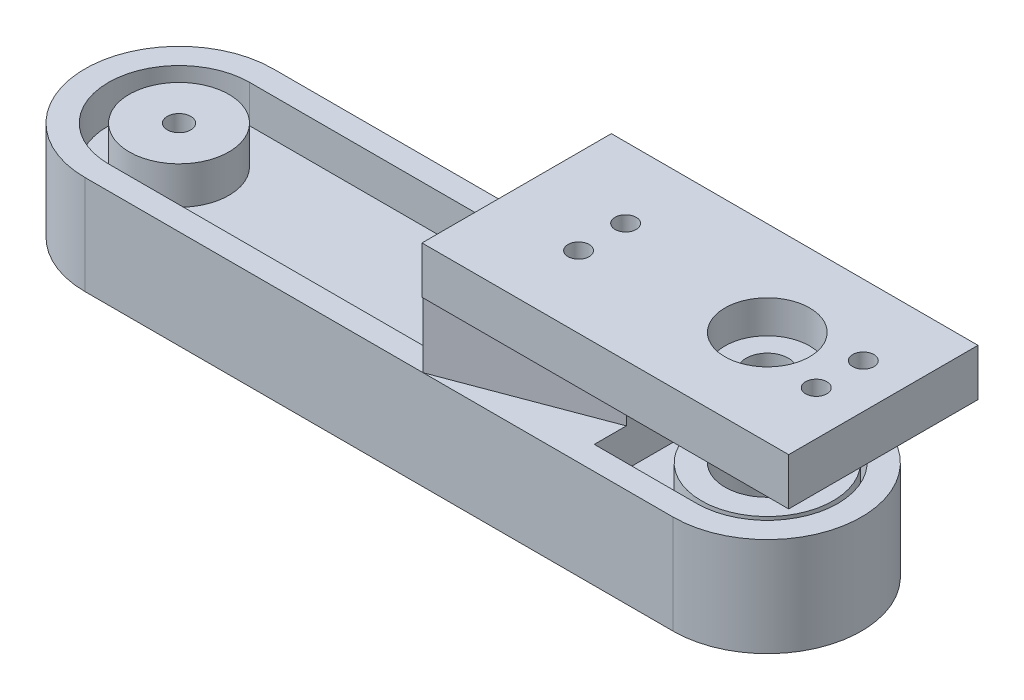
SolidWorks part; units mm, degrees
ref_plane "Front Plane" through (0, 0, 0) normal (0, 0, 1) x (1, 0, 0)
ref_plane "Top Plane" through (0, 0, 0) normal (0, 1, 0) x (1, 0, 0)
ref_plane "Right Plane" through (0, 0, 0) normal (1, 0, 0) x (0, 0, -1)
sketch "Sketch1" plane through (0, 0, 0) normal (0, 1, 0) x (1, 0, 0)
  line L0 (-62.5, 0) -> (62.5, 0) construction
  line L1 (-62.5, 30) -> (62.5, 30)
  line L2 (-62.5, -30) -> (62.5, -30)
  line L3 (-62.5, 0) -> (62.5, 0) construction
  line L4 (-62.5, 15) -> (62.5, 15)
  line L5 (-62.5, -15) -> (62.5, -15)
  arc A0 (-62.5, 30) -> (-62.5, -30) centre (-62.5, 0) ccw
  arc A1 (62.5, -30) -> (62.5, 30) centre (62.5, 0) ccw
  arc A2 (-62.5, 15) -> (-62.5, -15) centre (-62.5, 0) ccw
  arc A3 (62.5, -15) -> (62.5, 15) centre (62.5, 0) ccw
  point P3 (0, 0)
  point P8 (0, 0)
  dimension "D1" = 60
  dimension "D2" = 125
  dimension "D3" = 15
extrude "Boss-Extrude1" add sketch "Sketch1" along normal blind 25 contours L2 A1 L1 A0
sketch "Sketch4" plane through (0, 25, 0) normal (0, 1, 0) x (1, 0, 0)
  line L0 (-62.5, 30) -> (62.5, 30) construction
  circle A0 centre (-62.5, 0) radius 2.5
  dimension "D1" = 5
  dimension "D2" = 30
  dimension "D3" = 62.5
extrude "Cut-Extrude1" cut sketch "Sketch4" against normal through all
extrude "Cut-Extrude2" cut sketch "Sketch1<3>" against normal through all and the other way blind 10 contours L5 A3 L4 A2
sketch "Sketch1<3>" plane through (0, 0, 0) normal (0, 1, 0) x (1, 0, 0) same geometry as "Sketch1"
ref_plane "Plane1" through (0, 25, 0) normal (0, 1, 0) x (1, 0, 0)
sketch "Sketch7" plane through (0, 25, 0) normal (0, 1, 0) x (1, 0, 0)
  line L0 (-62.5, 0) -> (62.5, 0) construction
  line L1 (-62.5, 15) -> (62.5, 15)
  line L2 (-62.5, -15) -> (62.5, -15)
  line L3 (-62.5, 30) -> (62.5, 30) construction
  arc A0 (-62.5, 15) -> (-62.5, -15) centre (-62.5, 0) ccw
  arc A1 (62.5, -15) -> (62.5, 15) centre (62.5, 0) ccw
  point P4 (0, 0)
  dimension "D1" = 15
extrude "Cut-Extrude3" cut sketch "Sketch7" against normal blind 10
sketch "Sketch8" plane through (0, 10, 0) normal (0, -1, 0) x (-1, 0, 0)
  line L0 (-62.5, 15) -> (62.5, 15) construction
  circle A0 centre (-62.5, 0) radius 9
  dimension "D3" = 18
  dimension "D1" = 15
  dimension "D2" = 62.5
extrude "Cut-Extrude5" cut sketch "Sketch8" against normal through all
sketch "Sketch9" plane through (0, 15, 0) normal (0, 1, 0) x (1, 0, 0)
  circle A0 centre (-62.5, 0) radius 10.5959
  circle A1 centre (-62.5, 0) radius 2.5
sketch "Sketch10" plane through (0, 25, 0) normal (0, 1, 0) x (1, 0, 0)
  line L0 (-62.5, 20) -> (62.5, 20)
  line L1 (-62.5, -20) -> (62.5, -20)
  line L2 (-62.5, -30) -> (62.5, -30) construction
  line L3 (-62.5, 30) -> (62.5, 30) construction
  line L4 (-62.5, -30) -> (62.5, -30)
  line L5 (-62.5, 30) -> (62.5, 30)
  arc A0 (-62.5, 20) -> (-62.5, -20) centre (-62.5, 0) ccw
  arc A1 (62.5, -20) -> (62.5, 20) centre (62.5, 0) ccw
  arc A2 (-62.5, 30) -> (-62.5, -30) centre (-62.5, 0) ccw construction
  arc A3 (62.5, -30) -> (62.5, 30) centre (62.5, 0) ccw construction
  arc A4 (-62.5, 30) -> (-62.5, -30) centre (-62.5, 0) ccw
  arc A5 (62.5, -30) -> (62.5, 30) centre (62.5, 0) ccw
  dimension "D1" = 40
  dimension "D2" = 40
extrude "Cut-Extrude6" cut sketch "Sketch10" against normal up to next
sketch "Sketch11" plane through (0, 15, 0) normal (0, 1, 0) x (1, 0, 0)
  circle A0 centre (62.5, 0) radius 9
  circle A1 centre (62.5, 0) radius 14
  dimension "D1" = 28
  dimension "D2" = 18
extrude "Boss-Extrude3" add sketch "Sketch11" along normal blind 8 and the other way blind 14
extrude "Boss-Extrude4" add sketch "Sketch9" along normal blind 8 and the other way blind 14 contours A0
sketch "Sketch12" plane through (0, 1, 0) normal (0, -1, 0) x (1, 0, 0)
  circle A0 centre (-62.5, 0) radius 2.5
extrude "Cut-Extrude7" cut sketch "Sketch12" against normal through all
sketch "Sketch13" plane through (0, 25, 0) normal (0, 1, 0) x (1, 0, 0)
  line L1 (92.0948, 31.5917) -> (-101.7934, 31.5917)
  line L2 (92.0948, 31.5917) -> (92.0948, -40.9372)
  line L3 (92.0948, -40.9372) -> (-101.7934, -40.9372)
  line L4 (-101.7934, 31.5917) -> (-101.7934, -40.9372)
extrude "Cut-Extrude8" cut sketch "Sketch13" against normal blind 2
sketch "Sketch14" plane through (0, 0, 0) normal (0, -1, 0) x (1, 0, 0)
  line L1 (99.5163, 27.7947) -> (-99.2633, 27.7947)
  line L2 (99.5163, 27.7947) -> (99.5163, -35.2041)
  line L3 (99.5163, -35.2041) -> (-99.2633, -35.2041)
  line L4 (-99.2633, 27.7947) -> (-99.2633, -35.2041)
extrude "Cut-Extrude9" cut sketch "Sketch14" against normal blind 2
sketch "Sketch15" plane through (0, 15, 0) normal (0, 1, 0) x (1, 0, 0)
  line L0 (62.5, 20) -> (-62.5, 20) construction
  line L1 (40.7342, 20) -> (9.3613, 20)
  line L2 (40.7342, 20) -> (40.7342, -20)
  line L3 (40.7342, -20) -> (9.3613, -20)
  line L4 (9.3613, 20) -> (9.3613, -20)
  line L5 (-62.5, -20) -> (62.5, -20) construction
extrude "Boss-Extrude6" add sketch "Sketch15" along normal blind 22
sketch "Sketch16" plane through (0, 37, 0) normal (0, 1, 0) x (1, 0, 0)
  line L1 (9.3613, 20) -> (87.2738, 20)
  line L2 (9.3613, 20) -> (9.3613, -20.2336)
  line L3 (9.3613, -20.2336) -> (87.2738, -20.2336)
  line L4 (87.2738, 20) -> (87.2738, -20.2336)
extrude "Boss-Extrude7" add sketch "Sketch16" along normal blind 10
sketch "Sketch17" plane through (0, 37, 0) normal (0, -1, 0) x (1, 0, 0)
  circle A0 centre (62.5, 0) radius 9
  dimension "D1" = 18
extrude "Cut-Extrude10" cut sketch "Sketch17" against normal blind 10
sketch "Sketch18" plane through (0, 47, 0) normal (0, 1, 0) x (1, 0, 0)
  line L0 (27.4, -5) -> (27.4, 5) construction
  line L1 (62.5, 0) -> (15.5374, 0) construction
  line L2 (77.9, 5) -> (77.9, -5) construction
  circle A0 centre (27.4, 5) radius 2.25
  circle A1 centre (27.4, -5) radius 2.25
  circle A2 centre (77.9, 5) radius 2.25
  circle A3 centre (77.9, -5) radius 2.25
  point P7 (27.4, 0)
  dimension "D1" = 10
  dimension "D3" = 15.4
  dimension "D5" = 4.5
  dimension "D6" = 4.5
  dimension "D2" = 35.1
  dimension "D4" = 10
extrude "Cut-Extrude11" cut sketch "Sketch18" against normal blind 10
sketch "Sketch19" plane through (0, 23, 0) normal (0, 1, 0) x (1, 0, 0)
  line L0 (62.5, 0) -> (9.3613, 20)
  line L1 (9.3613, 20) -> (62.5, 20)
  line L2 (62.5, 20) -> (62.5, 0)
extrude "Cut-Extrude12" cut sketch "Sketch19" along normal blind 14
sketch "Sketch20" plane through (0, 23, 0) normal (0, 1, 0) x (1, 0, 0)
  line L0 (62.5, 0) -> (9.3613, -20)
  line L1 (9.3613, -20) -> (62.5, -20.2336)
  line L2 (9.3613, -20.2336) -> (87.2738, -20.2336) construction
  line L3 (62.5, -20.2336) -> (62.5, 0)
extrude "Cut-Extrude13" cut sketch "Sketch20" along normal blind 14
sketch "Sketch21" plane through (0, 37, 0) normal (0, -1, 0) x (1, 0, 0)
  circle A0 centre (62.5, 0) radius 9
  circle A1 centre (62.5, 0) radius 4.5
  dimension "D1" = 18
  dimension "D2" = 9
extrude "Boss-Extrude9" add sketch "Sketch21" against normal blind 3
